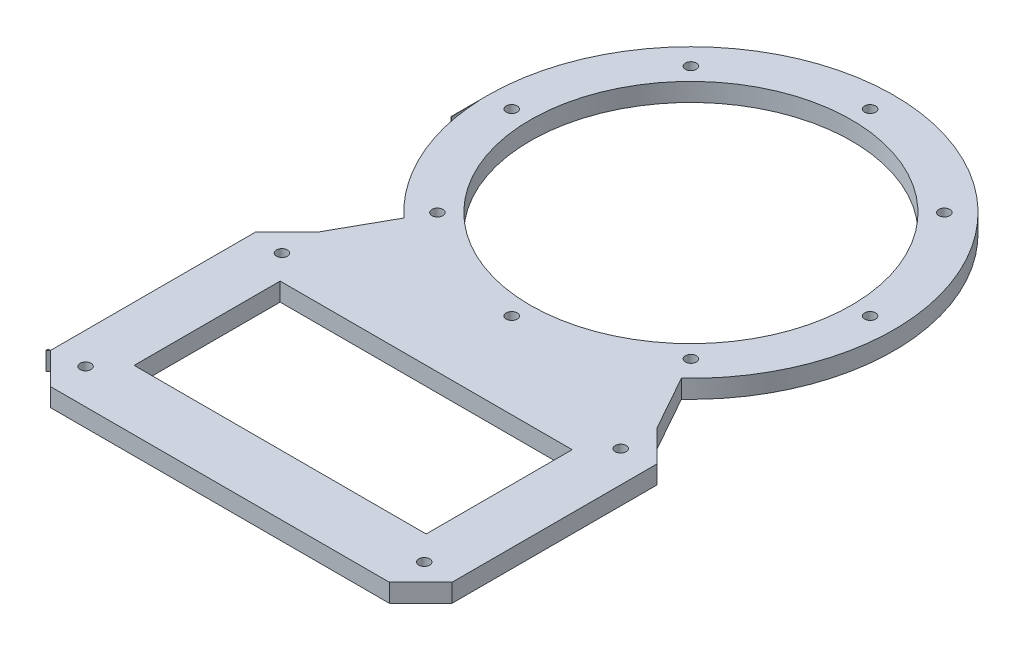
SolidWorks part; units mm, degrees
ref_plane "前视基准面" through (0, 0, 0) normal (0, 0, 1) x (1, 0, 0)
ref_plane "上视基准面" through (0, 0, 0) normal (0, 1, 0) x (1, 0, 0)
ref_plane "右视基准面" through (0, 0, 0) normal (1, 0, 0) x (0, 0, -1)
sketch "草图1" plane through (0, 0, 0) normal (0, 1, 0) x (1, 0, 0)
  line L1 (0, -55.6303) -> (-55, -55.6303)
  line L2 (-55, -55.6303) -> (-55, -129.0194)
  line L3 (-55, -129.0194) -> (55, -129.0194)
  line L10 (0, -55.6303) -> (55, -55.6303)
  line L11 (55, -55.6303) -> (55, -129.0194)
  line L12 (0, -65.6303) -> (-46.4, -65.6303)
  line L13 (-46.4, -65.6303) -> (-46.4, -119.4303)
  line L14 (-46.4, -119.4303) -> (46.4, -119.4303)
  line L15 (46.4, -119.4303) -> (46.4, -65.6303)
  line L16 (46.4, -65.6303) -> (0, -65.6303)
  line L17 (0, -72.5303) -> (40, -72.5303)
  line L18 (-46.4, -55.6303) -> (-55, -64.2303)
  line L19 (46.4, -55.6303) -> (55, -64.2303)
  line L20 (-46.4, -129.0194) -> (-55, -120.4194)
  line L21 (46.4, -129.0194) -> (55, -120.4194)
  line L22 (-46.4, -55.6303) -> (-38.0134, -40.6167)
  line L23 (46.4, -55.6303) -> (37.9494, -40.502)
  line L24 (40, -72.5303) -> (40, -112.5303)
  line L25 (40, -112.5303) -> (-40, -112.5303)
  line L26 (-40, -112.5303) -> (-40, -72.5303)
  line L27 (-40, -72.5303) -> (0, -72.5303)
  circle A1 centre (0, 0) radius 55.6303
  circle A2 centre (0, 0) radius 44
  circle A3 centre (-49.1, 0) radius 1.5
  circle A4 centre (-34.7189, 34.7189) radius 1.5
  circle A5 centre (0, 49.1) radius 1.5
  circle A6 centre (34.7189, 34.7189) radius 1.5
  circle A7 centre (49.1, 0) radius 1.5
  circle A8 centre (34.7189, -34.7189) radius 1.5
  circle A9 centre (0, -49.1) radius 1.5
  circle A10 centre (-34.7189, -34.7189) radius 1.5
  circle A15 centre (-46.4, -65.6303) radius 1.5
  circle A16 centre (46.4, -65.6303) radius 1.5
  circle A17 centre (-46.4, -119.4303) radius 1.5
  circle A18 centre (46.4, -119.4303) radius 1.5
  point P24 (0, 0)
  dimension "D1" = 8
extrude "凸台-拉伸1" add sketch "草图1" along normal blind 5 contours A1 A10 A9 A8 A7 A6 A5 A4 A3 A2 | A18 L15 A16 L16 L12 A15 L13 A17 L14 L26 L27 L17 L24 L25 | L3 L21 L11 L19 L10 L1 L18 L2 L20 A18 L14 A17 L13 A15 L12 L16 A16 L15 | A1 L22 L1 | A1 L10 L23 region at (23.2, 0, 56.9527) region at (31.919, 0, 51.0901) region at (-31.919, 0, 51.0901) region at (-19.8574, 0, 50.2775) region at (22.45, 0, 66.703)
sketch "草图3" plane through (0, 0, 0) normal (0, 1, 0) x (1, 0, 0)
  line L3 (-55, -64.2303) -> (-55.6268, 0.6268)
  line L4 (-63.6, -129.0194) -> (-55, -120.4194)
  line L5 (-63.6, -129.0194) -> (-123.6, -129.0194)
  line L6 (-123.6, -129.0194) -> (-132.2, -120.4194)
  line L7 (-132.2, -120.4194) -> (-132.2, 0)
  line L9 (-123.6, 67.7577) -> (-63.6, 67.7577)
  line L11 (-55, -64.2303) -> (-55, -120.4194)
  line L12 (-123.6, 67.7577) -> (-132.2, 59.1577)
  line L13 (-132.2, 59.1577) -> (-132.2, 0)
  line L14 (-63.6, 67.7577) -> (-55.6268, 59.7845)
  line L15 (-55.6268, 59.7845) -> (-55.6268, 0.6268)
  line L16 (-55.6268, 0.6268) -> (-53.5942, -2.9825)
  line L17 (-53.5942, -2.9825) -> (-41.0893, -28.2473)
  line L18 (-41.0893, -28.2473) -> (-35.6711, -39.1943)
  line L19 (-35.6711, -39.1943) -> (-41.0893, -57.3402)
  line L20 (-41.0893, -57.3402) -> (-55, -64.2303)
  line L21 (-53.5942, -2.9825) -> (-55.6268, 0.6268)
  arc A0 (38.0134, -40.6167) -> (-38.0134, -40.6167) centre (0, 0) ccw construction
  circle A1 centre (-93.6, -94.0194) radius 25
  circle A2 centre (-93.6, -94.0194) radius 30
  circle A3 centre (-93.6, -31.1527) radius 25
  circle A4 centre (-93.6, -31.1527) radius 30
  circle A5 centre (-123.6, 59.1577) radius 1.5
  circle A6 centre (-63.6, 59.7845) radius 1.5
  circle A7 centre (-123.6, -120.4194) radius 1.5
  circle A8 centre (-63.6, -120.4194) radius 1.5
  circle A9 centre (-93.6, 32.4083) radius 25
  circle A10 centre (-93.6, 32.4083) radius 30
extrude "凸台-拉伸2" add sketch "草图3" along normal blind 5 contours L11 L3 L9 L7 L6 L5 L4 A8 A7 A6 A5 A4 A2 | A4 | A2 | A10 region at (-57.1138, 0, 92.3249)
extrude "凸台-拉伸3" add sketch "草图3<5>" along normal blind 15 contours A4 A3 | A2 A1 | A10 | A9 region at (-122.7515, 0, 94.0194) region at (-122.7515, 0, 31.1527)
sketch "草图3<5>" plane through (0, 0, 0) normal (0, 1, 0) x (1, 0, 0) same geometry as "草图3"
sketch "草图4" plane through (0, 5, 0) normal (0, 1, 0) x (1, 0, 0)
  line L1 (-55.6268, 67.7577) -> (-180.1118, 67.7577)
  line L2 (-55.6268, 67.7577) -> (-55.6268, -136.0107)
  line L3 (-55.6268, -136.0107) -> (-180.1118, -136.0107)
  line L4 (-180.1118, 67.7577) -> (-180.1118, -136.0107)
extrude "切除-拉伸1" cut sketch "草图4" against normal blind 10 and the other way blind 10
sketch "草图5" plane through (0, 5, 0) normal (0, 1, 0) x (1, 0, 0)
  line L1 (-55, -120.4194) -> (-128.6234, -120.4194)
  line L2 (-55, -120.4194) -> (-55, -10.1002)
  line L3 (-55, -10.1002) -> (-128.6234, -10.1002)
  line L4 (-128.6234, -120.4194) -> (-128.6234, -10.1002)
  point P5 (-125.8782, -120.4194)
extrude "切除-拉伸2" cut sketch "草图5" against normal blind 10 contours L2 L1 L4 L3
